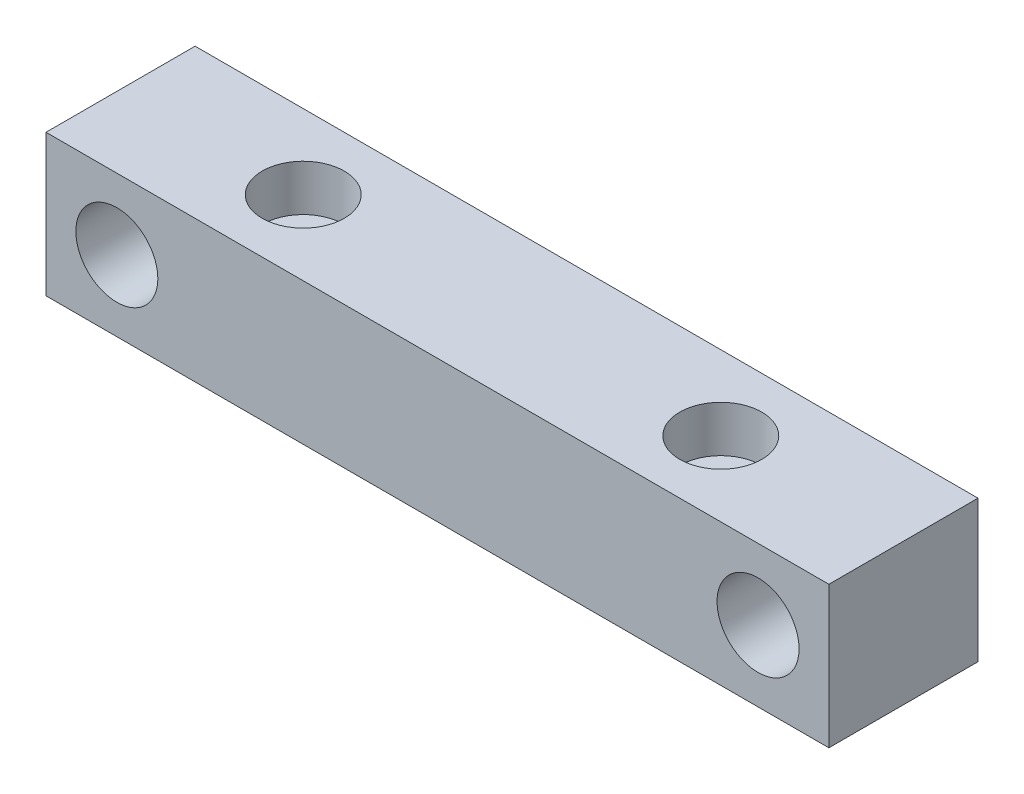
SolidWorks part; units mm, degrees
ref_plane "Front Plane" through (0, 0, 0) normal (0, 0, 1) x (1, 0, 0)
ref_plane "Top Plane" through (0, 0, 0) normal (0, 1, 0) x (1, 0, 0)
ref_plane "Right Plane" through (0, 0, 0) normal (1, 0, 0) x (0, 0, -1)
sketch "Sketch1" plane through (0, 0, 0) normal (0, 0, 1) x (1, 0, 0)
  line L2 (-51, -1.9987) -> (1.5, -1.9987)
  line L3 (-51, -1.9987) -> (-51, -11.4987)
  line L4 (-51, -11.4987) -> (1.5, -11.4987)
  line L5 (1.5, -1.9987) -> (1.5, -11.4987)
  line L6 (-46.25, -3.9987) -> (-46.25, -1.9987) construction
  line L7 (-49, -6.7487) -> (-51, -6.7487) construction
  line L8 (-46.25, -9.4987) -> (-46.25, -11.4987) construction
  line L9 (-0.5, -6.7487) -> (1.5, -6.7487) construction
  circle A0 centre (-46.25, -6.7487) radius 1.25 construction
  circle A1 centre (-3.25, -6.7487) radius 1.25 construction
  circle A8 centre (-3.25, -6.7487) radius 1.25 construction
  circle A9 centre (-46.25, -6.7487) radius 1.25 construction
  circle A10 centre (-46.25, -6.7487) radius 1.375
  circle A11 centre (-3.25, -6.7487) radius 1.375
  circle A12 centre (-46.25, -6.7487) radius 2.75 construction
  circle A13 centre (-3.25, -6.7487) radius 2.75 construction
  dimension "D1" = 2.75
  dimension "D3" = 5.5
  dimension "D2" = 2
extrude "Boss-Extrude1" add sketch "Sketch1" along normal blind 10
sketch "Sketch4" plane through (0, 0, 10) normal (0, 0, 1) x (1, 0, 0)
  circle A0 centre (-46.25, -6.7487) radius 1.375 construction
  circle A1 centre (-3.25, -6.7487) radius 1.375 construction
  circle A2 centre (-46.25, -6.7487) radius 1.375 construction
  circle A3 centre (-3.25, -6.7487) radius 1.375 construction
  circle A4 centre (-46.25, -6.7487) radius 2.75
  circle A5 centre (-3.25, -6.7487) radius 2.75
  dimension "D1" = 5.5
extrude "Cut-Extrude3" cut sketch "Sketch4" against normal offset from surface (7 mm away) 3
sketch "Sketch2" plane through (0, -1.9987, 0) normal (0, 1, 0) x (1, 0, 0)
  line L0 (-10.75, -3.625) -> (-10.75, 0) construction
  line L1 (1.5, 0) -> (-51, 0) construction
  line L2 (-10.75, -6.375) -> (-10.75, -10) construction
  line L3 (1.5, -10) -> (-51, -10) construction
  line L4 (-8, -5) -> (-6, -5) construction
  line L5 (-6, -3) -> (-6, -10) construction
  line L6 (-24.75, -10) -> (-24.75, 0) construction
  line L8 (-6, -3) -> (-6, -10) construction
  circle A0 centre (-10.75, -5) radius 1.375
  circle A1 centre (-10.75, -5) radius 2.75 construction
  circle A2 centre (-38.75, -5) radius 1.375
  circle A3 centre (-38.75, -5) radius 2.75 construction
  dimension "D2" = 2.75
  dimension "D3" = 5.5
  dimension "D1" = 2
extrude "Cut-Extrude1" cut sketch "Sketch2" against normal up to next
sketch "Sketch3" plane through (0, -1.9987, 0) normal (0, 1, 0) x (1, 0, 0)
  line L0 (-24.75, -10) -> (-24.75, 0) construction
  line L1 (1.5, -10) -> (-51, -10) construction
  line L2 (1.5, 0) -> (-51, 0) construction
  circle A0 centre (-38.75, -5) radius 1.375 construction
  circle A1 centre (-10.75, -5) radius 1.375 construction
  circle A2 centre (-10.75, -5) radius 1.375 construction
  circle A3 centre (-10.75, -5) radius 2.75
  circle A4 centre (-38.75, -5) radius 2.75
  dimension "D1" = 5.5
extrude "Cut-Extrude2" cut sketch "Sketch3" against normal blind 3.1
